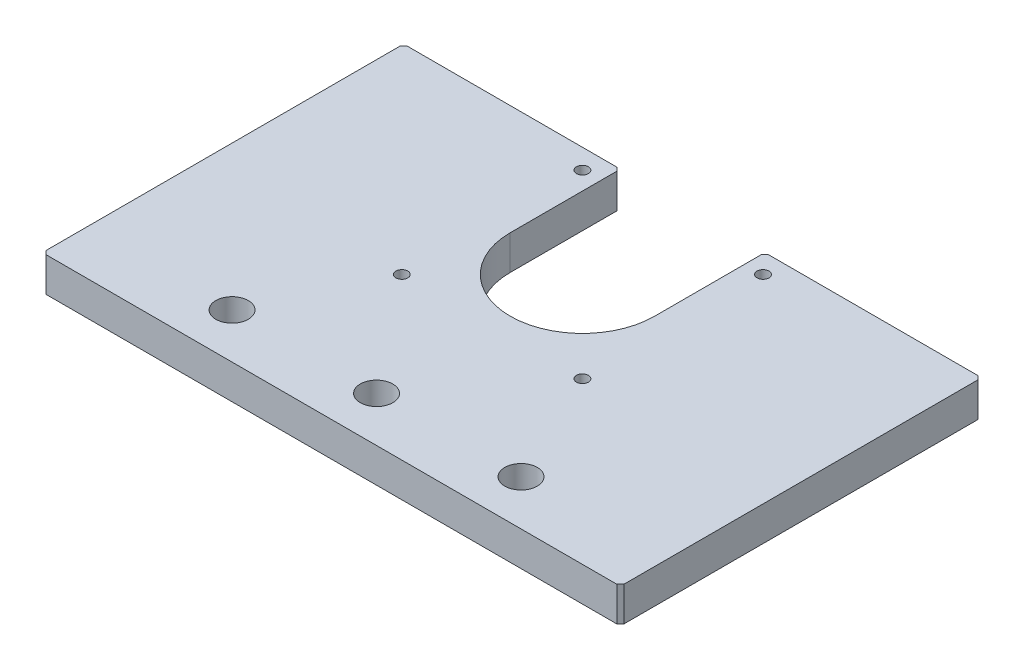
SolidWorks part; units mm, degrees
material "6061-T6 (SS)"
ref_plane "Front Plane" through (0, 0, 0) normal (0, 0, 1) x (1, 0, 0)
ref_plane "Top Plane" through (0, 0, 0) normal (0, 1, 0) x (1, 0, 0)
ref_plane "Right Plane" through (0, 0, 0) normal (1, 0, 0) x (0, 0, -1)
sketch "Sketch1" plane through (0, 0, 0) normal (0, 1, 0) x (1, 0, 0)
  line L0 (20, 0) -> (20, 30.5)
  line L1 (20, 30.5) -> (80, 30.5)
  line L2 (80, 30.5) -> (80, -69.5)
  line L3 (80, -69.5) -> (-80, -69.5)
  line L4 (-80, -69.5) -> (-80, 30.5)
  line L5 (-80, 30.5) -> (-20, 30.5)
  line L6 (-20, 30.5) -> (-20, 0)
  line L7 (-125.0932, -37) -> (-101.7391, -37) construction
  line L8 (-40, -57) -> (0, -57) construction
  line L9 (0, -57) -> (40, -57) construction
  line L10 (0, -5.2388) -> (0, 5.2388) construction
  line L12 (25, 25) -> (-25, 25) construction
  line L13 (25, 25) -> (25, -25) construction
  line L14 (25, -25) -> (-25, -25) construction
  line L15 (-25, 25) -> (-25, -25) construction
  line L16 (25, 25) -> (-25, -25) construction
  line L17 (25, -25) -> (-25, 25) construction
  arc A0 (-20, 0) -> (20, 0) centre (0, 0) ccw
  dimension "D1" = 20
  dimension "D7" = 50
  dimension "D2" = 37
  dimension "D3" = 40
  dimension "D4" = 20
  dimension "D5" = 100
  dimension "D6" = 67.5
  dimension "D8" = 12.5
  dimension "D9" = 160
  dimension "A" = 5.5
  dimension "B" = 55.5
  dimension "C" = 55
  dimension "D" = 105
extrude "Boss-Extrude1" add sketch "Sketch1" along normal mid plane 9.525
hole_wizard "M8 Clearance Hole1" positions "Sketch2" profile "Sketch3" hole size "M8" standard "ANSI Metric" end condition through all
sketch "Sketch2" plane through (0, 4.7625, 0) normal (0, 1, 0) x (1, 0, 0)
  point P0 (-40, -57)
  point P3 (0, -57)
  point P6 (40, -57)
sketch "Sketch3" plane through (-40, 4.7625, 57) normal (1, 0, 0) x (0, 0, 1)
  line L0 (0, 0) -> (0, 9.525)
  line L1 (0, 9.525) -> (4.5, 9.525)
  line L2 (4.5, 9.525) -> (4.5, 0)
  line L5 (4.5, 0) -> (0, 0)
  line L11 (0, -6.35) -> (0, 107.95) construction
  dimension "Thru Hole Dia." = 9
  dimension "Thru Hole Depth" = 9.525
hole_wizard "M4x0.7 Tapped Hole2" positions "Sketch4" profile "Sketch5" tap size "M4x0.7" standard "ANSI Metric" end condition up to next
sketch "Sketch4" plane through (0, 4.7625, 0) normal (0, 1, 0) x (1, 0, 0)
  point P0 (-25, -25)
  point P3 (-25, 25)
  point P6 (25, 25)
  point P9 (25, -25)
sketch "Sketch5" plane through (-25, 4.7625, 25) normal (1, 0, 0) x (0, 0, 1)
  line L0 (0, 0) -> (0, 9.525)
  line L1 (0, 9.525) -> (1.65, 9.525)
  line L2 (1.65, 9.525) -> (1.65, 0)
  line L5 (1.65, 0) -> (0, 0)
  line L11 (0, -6.35) -> (0, 107.95) construction
  dimension "Thru Tap Drill Dia." = 3.3
  dimension "Thru Tap Drill Depth" = 9.525
cosmetic thread "Hole Thread1" parameters "D2"=4
cosmetic thread "Hole Thread4" parameters "D2"=4
cosmetic thread "Hole Thread5" parameters "D2"=4
cosmetic thread "Hole Thread6" parameters "D2"=4
chamfer "Chamfer1" distance 1 6 edges at (-80, 0, -30.5) (-80, 0, 69.5) (80, 0, 69.5) (80, 0, -30.5) (-20, 0, -30.5) (20, 0, -30.5)
